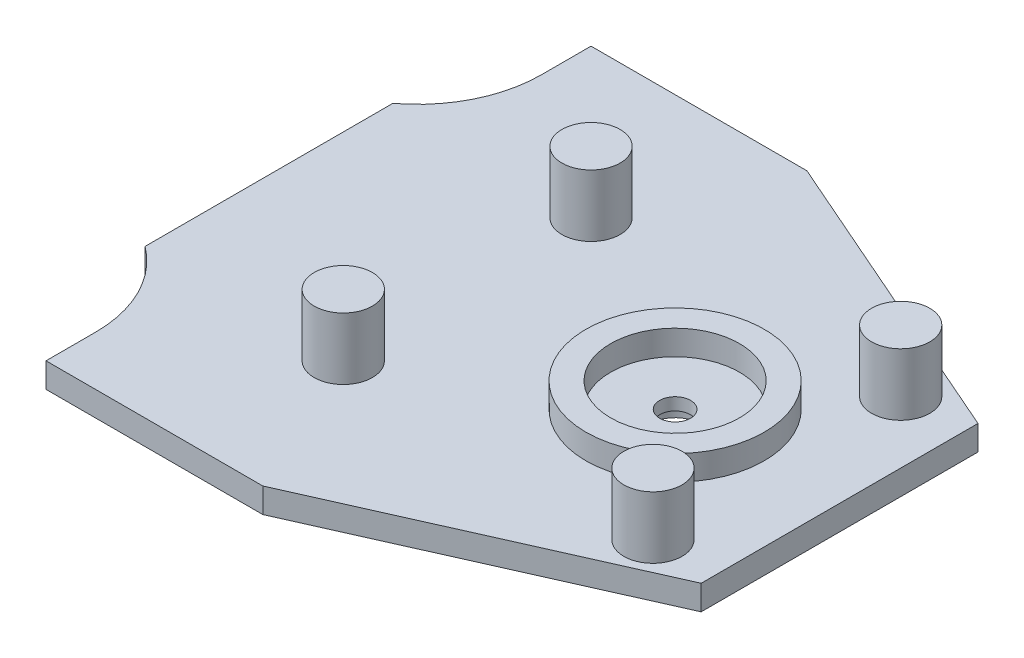
SolidWorks part; units mm, degrees
ref_plane "Front Plane" through (0, 0, 0) normal (0, 0, 1) x (1, 0, 0)
ref_plane "Top Plane" through (0, 0, 0) normal (0, 1, 0) x (1, 0, 0)
ref_plane "Right Plane" through (0, 0, 0) normal (1, 0, 0) x (0, 0, -1)
sketch "Sketch1" plane through (0, 0, 0) normal (0, 1, 0) x (1, 0, 0)
  line L0 (24.7807, 13.3351) -> (24.7807, -9.0149) construction
  line L2 (-21.2193, 12.0851) -> (-21.2193, -7.9149)
  line L4 (24.7807, 13.3262) -> (24.7807, -9.0238)
  line L5 (-21.2193, -7.9149) -> (-21.2193, 12.0851) construction
  line L6 (24.7807, 13.3262) -> (0.2093, 24.0851)
  line L7 (0.2093, 24.0851) -> (-17.2193, 24.0851)
  line L8 (-17.2193, 24.0851) -> (-17.2193, 12.0851)
  line L10 (-17.2193, 12.0851) -> (-21.2193, 12.0851)
  line L11 (-21.2193, 12.0851) -> (-21.2193, -7.9149)
  line L12 (-21.2193, -7.9149) -> (-17.2193, -7.9149)
  line L13 (-17.2193, -7.9149) -> (-17.2193, -19.9149)
  line L14 (-17.2193, -19.9149) -> (0.2863, -19.9149)
  line L15 (0.2863, -19.9149) -> (24.7807, -9.0238)
  dimension "D1" = 26.8065
extrude "Boss-Extrude2" add sketch "Sketch1" along normal blind 2 contours L14 L15 L4 L6 L7 L8 L10 L2 L12 L13 region at (0.6256, 0, -2.0949)
fillet "Fillet1" radius 10 2 edges at (-17.2193, 1, 7.9149) (-17.2193, 1, -12.0851)
sketch "Sketch3" plane through (0, 2, 0) normal (0, 1, 0) x (1, 0, 0)
  circle A0 centre (11.5685, 2.0851) radius 5.2
  circle A1 centre (11.5685, 2.0851) radius 7.2
  dimension "D1" = 10.4
  dimension "D2" = 2
extrude "Boss-Extrude3" add sketch "Sketch3" along normal blind 2
sketch "Sketch4" plane through (0, 0, 0) normal (0, -1, 0) x (1, 0, 0)
  circle A0 centre (11.5685, -2.0851) radius 1.25
  dimension "D1" = 2.5
extrude "Cut-Extrude1" cut sketch "Sketch4" against normal blind 2
sketch "Sketch5" plane through (0, 0, 0) normal (0, -1, 0) x (1, 0, 0)
  circle A0 centre (11.5685, -2.0851) radius 2
  dimension "D1" = 4
extrude "Cut-Extrude2" cut sketch "Sketch5" against normal blind 1
sketch "Sketch6" plane through (0, 2, 0) normal (0, 1, 0) x (1, 0, 0)
  circle A0 centre (19.7807, -7.9149) radius 2.35
  circle A1 centre (19.7807, 12.0851) radius 2.35
  circle A2 centre (-5.2193, -7.9149) radius 2.35
  circle A3 centre (-5.2193, 12.0851) radius 2.35
  dimension "D1" = 4.7
extrude "Boss-Extrude4" add sketch "Sketch6" along normal blind 5
